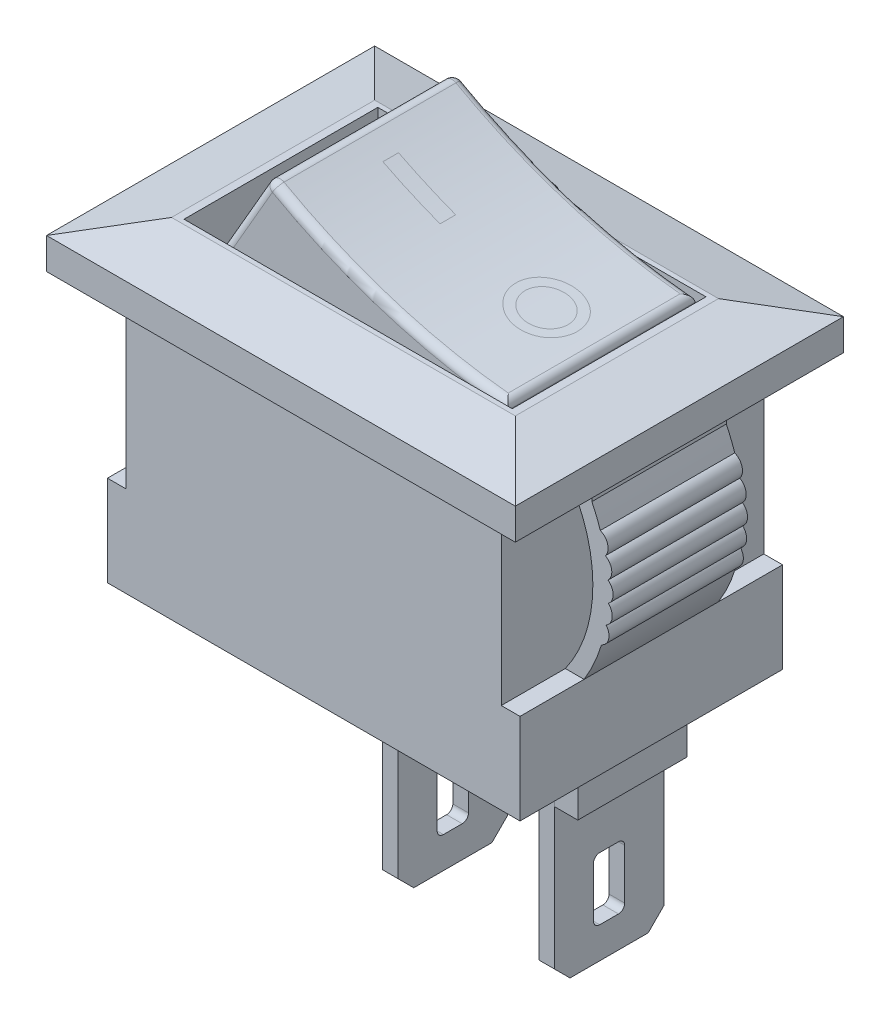
SolidWorks part; units mm, degrees
material "ABS"
ref_plane "Plano frontal" through (0, 0, 0) normal (0, 0, 1) x (1, 0, 0)
ref_plane "Plano superior" through (0, 0, 0) normal (0, 1, 0) x (1, 0, 0)
ref_plane "Plano direito" through (0, 0, 0) normal (1, 0, 0) x (0, 0, -1)
sketch "Esboço1" plane through (0, 0, 0) normal (0, 0, 1) x (1, 0, 0)
  line L1 (-6, 8.7) -> (6, 8.7)
  line L2 (-6, 8.7) -> (-6, 0)
  line L3 (-6, 0) -> (6, 0)
  line L4 (6, 8.7) -> (6, 0)
  dimension "D1" = 12
  dimension "D2" = 8.7
extrude "Ressalto-extrusão1" add sketch "Esboço1" along normal mid plane 8.4
sketch "Esboço2" plane through (0, 0, 0) normal (0, 0, 1) x (1, 0, 0)
  line L0 (0, 8.7) -> (0, 0) construction
  line L1 (-6.6, 2.9) -> (6.6, 2.9)
  line L2 (-6.6, 2.9) -> (-6.6, 0)
  line L3 (-6.6, 0) -> (6.6, 0)
  line L4 (6.6, 2.9) -> (6.6, 0)
  line L5 (6, 8.7) -> (-6, 8.7) construction
  line L6 (-6, 0) -> (6, 0) construction
  line L7 (-6.85, 8.7) -> (-6.4007, 8.7)
  line L8 (-6.6, 2.9) -> (-6, 2.9)
  line L10 (-6.4007, 7.7306) -> (-6.4007, 8.7)
  line L11 (-6, 8.7) -> (-6, 0) construction
  line L12 (-6.85, 7.95) -> (-6.85, 8.7)
  arc A0 (-6.6, 2.9) -> (-6.85, 7.95) centre (-2.144, 5.6518) cw construction
  arc A1 (-6, 2.9) -> (-6.4007, 7.7306) centre (-2.144, 5.6518) cw
  arc A2 (-6.407, 2.6096) -> (-6.85, 7.95) centre (-2.144, 5.6518) cw construction
  arc A3 (-7.12, 7.2852) -> (-7.282, 6.6664) centre (-6.9686, 6.9149) ccw
  arc A4 (-7.282, 6.6664) -> (-7.3673, 6.0325) centre (-7.0866, 6.3174) ccw
  arc A5 (-7.3748, 5.3928) -> (-7.3042, 4.7571) centre (-7.1007, 5.1015) ccw
  arc A6 (-7.3673, 6.0325) -> (-7.3748, 5.3928) centre (-7.1309, 5.7098) ccw
  arc A7 (-7.3042, 4.7571) -> (-7.1566, 4.1347) centre (-6.9967, 4.5013) ccw
  arc A8 (-6.2035, 2.7548) -> (-6.6254, 7.8403) centre (-2.144, 5.6518) cw construction
  arc A9 (-7.12, 7.2852) -> (-6.85, 7.95) centre (-2.144, 5.6518) cw
  arc A10 (-7.1566, 4.1347) -> (-6.6, 2.9) centre (-2.144, 5.6518) ccw
  point P8 (0, 0)
  dimension "D3" = 0.5
  dimension "D6" = 0.4
  dimension "D7" = 0.25
  dimension "D1" = 13.2
  dimension "D2" = 13.7
  dimension "D4" = 5.8
  dimension "D5" = 0.75
extrude "Ressalto-extrusão2" add sketch "Esboço2" along normal up to vertex (4.2 mm away) and the other way up to vertex (4.2 mm away) contours L2 L3 L4 L1 up to point (-6, 8.7, 4.2) other way up to point (-6, 8.7, -4.2)
extrude "Ressalto-extrusão3" add sketch "Esboço2<3>" along normal mid plane 4.3 contours A7 A10 L1 A1 L10 L7 L12 A9 A3 A4 A6 A5 region at (-6.9145, 5.7207, 0)
sketch "Esboço2<3>" plane through (0, 0, 0) normal (0, 0, 1) x (1, 0, 0) same geometry as "Esboço2"
mirror "Espelhar1" about plane through (0, 0, 0) normal (1, 0, 0) of "Ressalto-extrusão3"
sketch "Esboço3" plane through (0, 8.7, 0) normal (0, 1, 0) x (1, 0, 0)
  line L0 (0, 5.25) -> (0, -5.25) construction
  line L1 (-7.5, 5.25) -> (7.5, 5.25)
  line L2 (-7.5, 5.25) -> (-7.5, -5.25)
  line L3 (-7.5, -5.25) -> (7.5, -5.25)
  line L4 (7.5, 5.25) -> (7.5, -5.25)
  dimension "D1" = 15
  dimension "D2" = 10.5
extrude "Ressalto-extrusão4" add sketch "Esboço3" along normal blind 1.5
sketch "Esboço7" plane through (7.5, 0, 0) normal (1, 0, 0) x (0, 0, -1)
  line L0 (5.25, 9.7) -> (3.25, 10.2)
  line L1 (5.25, 10.2) -> (5.25, 8.7) construction
  line L2 (-5.25, 10.2) -> (5.25, 10.2) construction
  line L3 (3.25, 10.2) -> (5.5253, 10.7947)
  line L4 (0, 10.2) -> (0, 8.7) construction
  line L5 (5.5253, 10.7947) -> (5.25, 9.7)
  line L6 (-5.25, 8.7) -> (5.25, 8.7) construction
  line L7 (-5.25, 9.7) -> (-3.25, 10.2)
  line L8 (-3.25, 10.2) -> (-5.5253, 10.7947)
  line L9 (-5.5253, 10.7947) -> (-5.25, 9.7)
  dimension "D1" = 1
  dimension "D2" = 2
extrude "Corte-extrusão1" cut sketch "Esboço7" against normal through all
sketch "Esboço8" plane through (0, 0, -5.25) normal (0, 0, -1) x (-1, 0, 0)
  line L0 (-7.5, 9.7) -> (-5.5, 10.2)
  line L1 (-7.5, 9.7) -> (-7.5, 8.7) construction
  line L2 (7.5, 10.2) -> (-7.5, 10.2) construction
  line L3 (-5.5, 10.2) -> (-8.0587, 11.1225)
  line L4 (-8.0587, 11.1225) -> (-7.5, 9.7)
  line L5 (0, 10.2) -> (0, 8.7) construction
  line L6 (-6, 8.7) -> (6, 8.7) construction
  line L7 (8.0587, 11.1225) -> (7.5, 9.7)
  line L8 (5.5, 10.2) -> (8.0587, 11.1225)
  line L9 (7.5, 9.7) -> (5.5, 10.2)
  dimension "D1" = 2
extrude "Corte-extrusão2" cut sketch "Esboço8" against normal through all
sketch "Esboço9" plane through (0, 10.2, 0) normal (0, 1, 0) x (1, 0, 0)
  line L0 (0, 3.1) -> (0, -3.1) construction
  line L1 (-5.25, -3.1) -> (5.25, -3.1)
  line L2 (-5.25, -3.1) -> (-5.25, 3.1)
  line L3 (-5.25, 3.1) -> (5.25, 3.1)
  line L4 (5.25, -3.1) -> (5.25, 3.1)
  dimension "D1" = 10.5
  dimension "D2" = 6.2
split line "Linha de divisão7"
sketch "Esboço10" plane through (0, 0, 0) normal (0, 0, 1) x (1, 0, 0)
  line L0 (-4, 10.2) -> (-2.6144, 12.6)
  line L1 (5.5, 10.2) -> (-5.5, 10.2) construction
  line L2 (5, 10.2) -> (-4, 10.2)
  arc A0 (-2.6144, 12.6) -> (5, 10.2) centre (6.6032, 28.5653) ccw
  dimension "D1" = 1.5
  dimension "D2" = 2.4
  dimension "D3" = 60
  dimension "D4" = 0.5
extrude "Ressalto-extrusão5" add sketch "Esboço10" against normal blind 3 and the other way blind 3
sketch "Esboço16" plane through (0, 10.2, 0) normal (0, 1, 0) x (1, 0, 0)
  line L4 (-5.25, 3.1) -> (-5.25, -3.1)
  line L9 (-5.25, -3.1) -> (5.25, -3.1)
  line L11 (5.25, -3.1) -> (5.25, 3.1)
  line L12 (5.25, 3.1) -> (-5.25, 3.1)
  line L13 (-5.25, 3.1) -> (-5.25, -3.1)
  line L14 (-5.25, -3.1) -> (5.25, -3.1)
  line L15 (5.25, -3.1) -> (5.25, 3.1)
  line L16 (5.25, 3.1) -> (-5.25, 3.1)
  line L23 (-2.6144, 3) -> (-4, 3) construction
  line L24 (-4, 3) -> (-4, -3) construction
  line L25 (-4, -3) -> (-2.6144, -3) construction
  line L26 (5, -3) -> (5, 3) construction
  line L27 (5, 3) -> (-2.6144, 3) construction
  line L28 (-2.6144, -3) -> (5, -3) construction
  line L29 (-2.6144, 3) -> (-4, 3)
  line L30 (-4, 3) -> (-4, -3)
  line L31 (-4, -3) -> (-2.6144, -3)
  line L32 (5, -3) -> (5, 3)
  line L33 (5, 3) -> (-2.6144, 3)
  line L34 (-2.6144, -3) -> (5, -3)
  line M1 (-5.25, -3.1) -> (5.25, -3.1)
  line M4 (-4, -3) -> (-4, 3)
  dimension "D1" = 0
extrude "Corte-extrusão4" cut sketch "Esboço16" against normal blind 5 contours M1 M4 region at (0, 10.2, -3.0878)
fillet "Filete1" radius 0.25 6 edges at (-2.6144, 12.6, 0) (-3.3072, 11.4, -3) (1.0613, 10.9829, -3) (-3.3072, 11.4, 3) (1.0613, 10.9829, 3) (5, 10.2, 0)
sketch "Esboço11" plane through (0, 0, 0) normal (0, -1, 0) x (1, 0, 0)
  line L0 (0.25, 1.75) -> (1, 1.75)
  line L1 (-1, -1.75) -> (-0.25, -1.75)
  line L2 (-1, -1.75) -> (-1, 1.75)
  line L3 (-1, 1.75) -> (-0.25, 1.75)
  line L4 (1, -1.75) -> (1, 1.75)
  line L5 (-1, -1.75) -> (1, 1.75) construction
  line L6 (-1, 1.75) -> (1, -1.75) construction
  line L8 (-0.25, -1.75) -> (-0.25, 1.75)
  line L9 (0.25, -1.75) -> (1, -1.75)
  line L10 (0.25, -1.75) -> (0.25, 1.75)
  line L11 (-0.25, -1.75) -> (0.25, 1.75) construction
  line L12 (-0.25, 1.75) -> (0.25, -1.75) construction
  point P0 (0, 0)
  point P6 (0, 0)
  dimension "D1" = 3.5
  dimension "D2" = 2
  dimension "D3" = 0.5
extrude "Ressalto-extrusão6" add sketch "Esboço11" along normal blind 1.5
sketch "Esboço12" plane through (0, 0, 0) normal (0, -1, 0) x (1, 0, 0)
  line L0 (-0.25, 1.75) -> (-1, 1.75) construction
  line L1 (-0.25, -1.75) -> (0.25, -1.75)
  line L2 (-0.25, -1.75) -> (-0.25, 1.75)
  line L3 (-0.25, 1.75) -> (0.25, 1.75)
  line L4 (0.25, -1.75) -> (0.25, 1.75)
  line L5 (-0.25, -1.75) -> (0.25, 1.75) construction
  line L6 (-0.25, 1.75) -> (0.25, -1.75) construction
  point P0 (0, 0)
  dimension "D1" = 0.5
extrude "Ressalto-extrusão7" add sketch "Esboço12" along normal blind 6.5
sketch "Esboço13" plane through (-0.25, 0, 0) normal (-1, 0, 0) x (0, 0, 1)
  line L0 (1.75, -6.5) -> (-1.75, -6.5) construction
  line L1 (-0.3, -3.5) -> (0.3, -3.5)
  line L2 (-0.5, -3.7) -> (-0.5, -5.3)
  line L3 (-0.3, -5.5) -> (0.3, -5.5)
  line L4 (0.5, -3.7) -> (0.5, -5.3)
  line L5 (0, -6.5) -> (0, 0) construction
  arc A0 (-0.5, -5.3) -> (-0.3, -5.5) centre (-0.3, -5.3) ccw
  arc A1 (0.3, -5.5) -> (0.5, -5.3) centre (0.3, -5.3) ccw
  arc A2 (0.5, -3.7) -> (0.3, -3.5) centre (0.3, -3.7) ccw
  arc A3 (-0.3, -3.5) -> (-0.5, -3.7) centre (-0.3, -3.7) ccw
  point P9 (0, -3.5)
  point P14 (0.5, -5.5)
  point P17 (0.5, -3.5)
  point P20 (-0.5, -3.5)
  dimension "D4" = 0.2
  dimension "D1" = 1
  dimension "D2" = 2
  dimension "D3" = 1
extrude "Corte-extrusão3" cut sketch "Esboço13" against normal up to vertex (0.5 mm away) up to point (0.25, -1.5, -1.75)
chamfer "Chanfro1" distance 0.5 angle 45 2 edges at (0, -6.5, 1.75) (0, -6.5, -1.75)
pattern_linear "Padrão linear1" count 2 spacing 5 along (1, 0, 0) of "Ressalto-extrusão7", "Corte-extrusão3", "Chanfro1", "Ressalto-extrusão6"
pattern_linear "Padrão linear2" count 2 spacing 5 along (-1, 0, 0) of "Ressalto-extrusão6"
sketch "Esboço15" plane through (0, 0, 1.75) normal (0, 0, 1) x (1, 0, 0)
  line L0 (0.25, -1.5) -> (0.25, 0)
  line L1 (1, 0) -> (-1, 0) construction
  line L2 (-0.25, -1.5) -> (-0.25, 0)
  line L3 (4.75, -1.5) -> (4.75, 0)
  line L4 (6, 0) -> (4, 0) construction
  line L5 (5.25, -1.5) -> (5.25, 0)
split line "Linha de divisão8"
sketch "Esboço17" plane through (-4, 0, 0) normal (-1, 0, 0) x (0, 0, 1)
  line L4 (2.75, 10.2) -> (-2.75, 10.2)
  line L5 (-3, 9.7) -> (-3, 5.2)
  line L6 (-3, 5.2) -> (3, 5.2)
  line L7 (3, 5.2) -> (3, 9.7)
  line L8 (2.75, 10.2) -> (-2.75, 10.2)
  line L9 (-3, 9.7) -> (-3, 5.2)
  line L10 (-3, 5.2) -> (3, 5.2)
  line L11 (3, 5.2) -> (3, 9.7)
  ellipse E2 centre (-2.75, 9.7) end of major axis (-2.75, 9.2) minor radius 0.25 (-2.75, 10.2) -> (-3, 9.7) ccw
  ellipse E3 centre (2.75, 9.7) end of major axis (2.75, 10.2) minor radius 0.25 (3, 9.7) -> (2.75, 10.2) ccw
  ellipse E4 centre (-2.75, 9.7) end of major axis (-2.75, 9.2) minor radius 0.25 (-2.75, 10.2) -> (-3, 9.7) ccw
  ellipse E5 centre (2.75, 9.7) end of major axis (2.75, 10.2) minor radius 0.25 (3, 9.7) -> (2.75, 10.2) ccw
  dimension "D1" = 0
extrude "Ressalto-extrusão8" add sketch "Esboço17" along direction (-0.5, -0.866, 0) on the side of the normal up to next (1.25 mm away)
ref_plane "Plano1" through (11.5809, 46.3235, 0) normal (-0.2425, -0.9701, 0) x (0.9701, -0.2425, 0)
sketch "Esboço14" plane through (11.5809, 46.3235, 0) normal (-0.2425, -0.9701, 0) x (0.9701, -0.2425, 0)
  line L0 (4.9235, 0) -> (-9.6287, 0) construction
  line L1 (-2.6605, 0.25) -> (-4.6605, 0.25)
  line L2 (-2.6605, 0.25) -> (-2.6605, -0.25)
  line L3 (-2.6605, -0.25) -> (-4.6605, -0.25)
  line L4 (-4.6605, 0.25) -> (-4.6605, -0.25)
  line L5 (4.9235, 5.25) -> (4.9235, -5.25) construction
  line L6 (-9.6287, 5.25) -> (-9.6287, -5.25) construction
  line L7 (-5.6605, 2.75) -> (-5.6605, -2.75) construction
  line L8 (2.6194, -3.1) -> (2.6194, 3.1) construction
  circle A0 centre (0.6194, 0) radius 1
  circle A1 centre (0.6194, 0) radius 0.7
  point P13 (-4.6605, 0)
  dimension "D4" = 0.3
  dimension "D1" = 0.5
  dimension "D2" = 2
  dimension "D3" = 1
  dimension "D6" = 2
wrap "Envolver1" sketch "Esboço14" wrap type scribe source sketch "Esboço14" face at (1.1293, 11.1647, 0)
